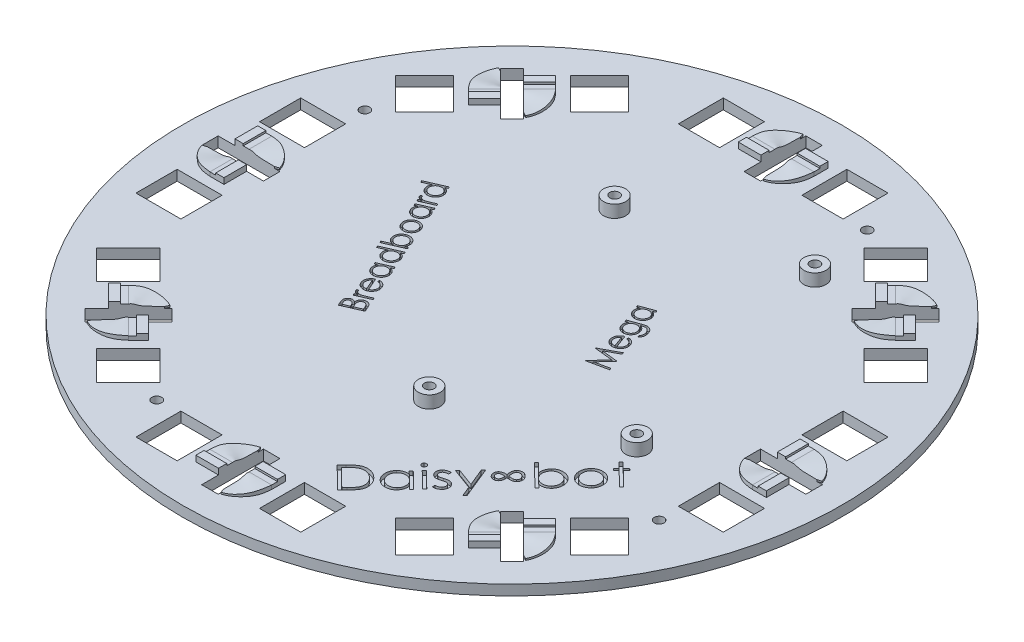
SolidWorks part; units mm, degrees
ref_plane "Front" through (0, 0, 0) normal (0, 0, 1) x (1, 0, 0)
ref_plane "Top" through (0, 0, 0) normal (0, 1, 0) x (1, 0, 0)
ref_plane "Right" through (0, 0, 0) normal (1, 0, 0) x (0, 0, -1)
sketch "Sketch1" plane through (0, 0, 0) normal (0, 1, 0) x (1, 0, 0)
  circle A0 centre (0, 0) radius 101.6
  dimension "D1" = 203.2
extrude "Boss-Extrude1" add sketch "Sketch1" along normal blind 3.175 contours A0
sketch "Sketch2" plane through (0, 3.175, 0) normal (0, 1, 0) x (1, 0, 0)
  line L1 (-2.54, -93.1333) -> (2.54, -93.1333)
  line L2 (-2.54, -93.1333) -> (-2.54, -74.0833)
  line L3 (-2.54, -74.0833) -> (2.54, -74.0833)
  line L4 (2.54, -93.1333) -> (2.54, -74.0833)
  point P4 (0, -74.0833)
  dimension "D1" = 5.08
  dimension "D2" = 19.05
  dimension "D3" = 93.1333
extrude "Cut-Extrude1" cut sketch "Sketch2" against normal up to next and the other way through all contours L1 L4 L3 L2
sketch "Sketch4" plane through (0, 3.175, 0) normal (0, 1, 0) x (1, 0, 0)
  line L0 (0, -83.6083) -> (-2.9434, -74.5495) construction
  line L1 (-2.9434, -74.5495) -> (0, -83.6083) construction
  line L2 (0, -83.6083) -> (-5.5987, -75.9024) construction
  line L3 (0, -83.6083) -> (-7.7059, -78.0097) construction
  line L4 (0, -83.6083) -> (-9.0588, -80.6649) construction
  line L5 (0, -83.6083) -> (-9.525, -83.6083) construction
  line L9 (2.54, -74.0833) -> (-2.54, -74.0833) construction
  line L10 (2.54, -74.0833) -> (2.54, -93.1333) construction
  line L11 (-2.54, -74.0833) -> (-2.54, -93.1333) construction
  line L12 (2.54, -93.1333) -> (-2.54, -93.1333) construction
  circle A0 centre (0, -83.6083) radius 9.525 construction
  point P16 (0, -74.0833)
  point P19 (2.54, -83.6083)
  dimension "D1" = 18
  dimension "D2" = 18
  dimension "D3" = 18
  dimension "D4" = 18
  dimension "D5" = 18
ref_plane "Plane1" through (-24.5719, 0, 7.9839) normal (0.9511, 0, -0.309) x (-0.309, 0, -0.9511)
ref_plane "Plane2" through (-39.7581, 0, 28.886) normal (0.809, 0, -0.5878) x (-0.5878, 0, -0.809)
ref_plane "Plane3" through (-39.7581, 0, 54.7224) normal (0.5878, 0, -0.809) x (-0.809, 0, -0.5878)
ref_plane "Plane4" through (-24.5719, 0, 75.6244) normal (0.309, 0, -0.9511) x (-0.9511, 0, -0.309)
ref_plane "Plane5" through (0, 0, 83.6083) normal (0, 0, -1) x (-1, 0, 0)
sketch "Sketch5" plane through (-24.5719, 0, 7.9839) normal (0.9511, 0, -0.309) x (-0.309, 0, -0.9511)
  line L0 (-69.6725, 3.175) -> (-87.7902, 3.175) construction
  line L1 (-71.2966, 3.175) -> (-69.9913, 3.175)
  line L2 (-71.2966, 3.175) -> (-71.2966, 3.683)
  line L3 (-71.2966, 3.683) -> (-69.9913, 3.683)
  line L4 (-69.9913, 3.175) -> (-69.9913, 3.683)
  dimension "D2" = 0.508
sketch "Sketch6" plane through (-39.7581, 0, 28.886) normal (0.809, 0, -0.5878) x (-0.5878, 0, -0.809)
  line L0 (-58.4417, 3.175) -> (-73.8535, 3.175) construction
  line L1 (-63.3193, 3.175) -> (-58.1156, 3.175)
  line L2 (-63.3193, 3.175) -> (-63.3193, 3.775)
  line L3 (-63.3193, 3.775) -> (-58.1156, 3.775)
  line L4 (-58.1156, 3.175) -> (-58.1156, 3.775)
  dimension "D2" = 0.6
sketch "Sketch7" plane through (-39.7581, 0, 54.7224) normal (0.5878, 0, -0.809) x (-0.809, 0, -0.5878)
  line L0 (-41.4902, 3.175) -> (-52.6875, 3.175) construction
  line L1 (-46.0041, 3.175) -> (-39.6187, 3.175)
  line L2 (-46.0041, 3.175) -> (-46.0041, 4.075)
  line L3 (-46.0041, 4.075) -> (-39.6187, 4.075)
  line L4 (-39.6187, 3.175) -> (-39.6187, 4.075)
  dimension "D2" = 0.9
sketch "Sketch10" plane through (-24.5719, 0, 75.6244) normal (0.309, 0, -0.9511) x (-0.9511, 0, -0.309)
  line L0 (-25.8364, 3.175) -> (-16.7776, 3.175) construction
  line L1 (-23.1657, 3.175) -> (-16.3114, 3.175)
  line L2 (-23.1657, 3.175) -> (-23.1657, 4.375)
  line L3 (-23.1657, 4.375) -> (-16.3114, 4.375)
  line L4 (-16.3114, 3.175) -> (-16.3114, 4.375)
  dimension "D3" = 1.2
sketch "Sketch11" plane through (0, 0, 83.6083) normal (0, 0, -1) x (-1, 0, 0)
  line L0 (0, 3.175) -> (9.525, 3.175) construction
  line L1 (2.54, 3.175) -> (9.525, 3.175)
  line L2 (2.54, 3.175) -> (2.54, 4.375)
  line L3 (2.54, 4.375) -> (9.525, 4.375)
  line L4 (9.525, 3.175) -> (9.525, 4.375)
  dimension "D3" = 1.2
loft "Loft1" add profiles "Sketch5", "Sketch6", "Sketch7", "Sketch10", "Sketch11" connector at (-2.54, 3.683, 75.791) connector at (-2.54, 3.775, 80.1123) connector at (-2.54, 4.075, 81.7629) connector at (-2.54, 4.375, 82.783) connector at (-2.54, 4.375, 83.6083)
sketch "Sketch13" plane through (-104.9799, 0, 83.6083) normal (0, 0, -1) x (-1, 0, 0)
  line L6 (-95.4549, 3.175) -> (-102.4399, 3.175)
  line L7 (-95.4549, 3.175) -> (-95.4549, 4.375)
  line L8 (-95.4549, 4.375) -> (-102.4399, 4.375)
  line L9 (-102.4399, 3.175) -> (-102.4399, 4.375)
extrude "Boss-Extrude4" add sketch "Sketch13" against normal blind 1.7907
sketch "Sketch25" plane through (0, 0, 85.399) normal (0, 0, 1) x (1, 0, 0)
  line L0 (-9.525, 4.375) -> (-2.54, 4.375) construction
  line L1 (-9.525, 3.175) -> (-2.54, 3.175)
  line L2 (-9.525, 3.175) -> (-9.525, 4.975)
  line L3 (-9.525, 4.975) -> (-2.54, 4.975)
  line L4 (-2.54, 3.175) -> (-2.54, 4.975)
  dimension "D1" = 0.6
extrude "Boss-Extrude5" add sketch "Sketch25" along normal blind 2.54
sketch "Sketch14" plane through (-2.54, 0, 0) normal (1, 0, 0) x (0, 0, -1)
  line L0 (-83.6083, 3.175) -> (-83.6083, 0) construction
  line L1 (-74.0833, 0) -> (-93.1333, 0) construction
ref_plane "Plane6" through (0, 0, 0) normal (1, 0, 0) x (0, 0, -1)
sketch "Sketch15" plane through (0, 0, 0) normal (1, 0, 0) x (0, 0, -1)
  line L0 (-83.6083, 0) -> (-83.6083, 3.175) construction
pattern_circular "CirPattern1" count 2 over 360 about axis through (0, 0, 83.6083) along (0, 1, 0) of "Loft1", "Boss-Extrude5", "Boss-Extrude4" reverse direction yes
ref_axis "Axis1" through (0, 50, 0) along (0, -1, 0)
pattern_circular "CirPattern5" count 8 over 360 about axis through (0, 50, 0) along (0, -1, 0) of "CirPattern1", "Cut-Extrude1"
sketch "Sketch18" plane through (0, 3.175, 0) normal (0, 1, 0) x (1, 0, 0)
  line L0 (-12.3739, 44.0137) -> (36.5149, 57.7582) construction
  line L1 (-12.3739, 44.0137) -> (9.9679, -35.4555) construction
  line L2 (36.5149, 57.7582) -> (36.8586, 56.5356) construction
  line L3 (54.6967, -16.2402) -> (8.2378, -29.3015) construction
  line L4 (0, -101.6) -> (0, 101.6) construction
  line L5 (0, -1.7463) -> (0, 1.7463) construction
  line L6 (-101.6, 0) -> (101.6, 0) construction
  line L7 (36.8586, 56.5356) -> (54.6967, -16.2402) construction
  circle A0 centre (-12.3739, 44.0137) radius 3.405
  circle A1 centre (9.9679, -35.4555) radius 3.405
  circle A2 centre (54.6967, -16.2402) radius 3.405
  circle A3 centre (36.8586, 56.5356) radius 3.405
  circle A4 centre (9.9679, -35.4555) radius 1.5
  circle A5 centre (-12.3739, 44.0137) radius 1.5
  circle A6 centre (36.8586, 56.5356) radius 1.5
  circle A7 centre (54.6967, -16.2402) radius 1.5
  circle A8 centre (0, 0) radius 101.6 construction
  dimension "D7" = 1.905
  dimension "D8" = 3
  dimension "D9" = 1.27
  dimension "D1" = 82.55
  dimension "D2" = 74.93
  dimension "D3" = 50.8
  dimension "D4" = 15.703
  dimension "D5" = 36.83
  dimension "D10" = 48.26
sketch "Sketch19" plane through (0, 3.175, 0) normal (0, 1, 0) x (1, 0, 0)
  line L0 (-32.0765, -77.4396) -> (0, 0) construction
  line L1 (0, -101.6) -> (0, 101.6) construction
  circle A1 centre (-32.0765, -77.4396) radius 1.5
  circle A4 centre (0, 0) radius 101.6 construction
  dimension "D4" = 3
  dimension "D6" = 83.82
  dimension "D5" = 22.5
extrude "Cut-Extrude2" cut sketch "Sketch19" against normal through all
pattern_circular "CirPattern7" count 4 over 360 about axis through (0, 50, 0) along (0, -1, 0) of "Cut-Extrude2"
extrude "Boss-Extrude3" add sketch "Sketch18" along normal blind 3.81
sketch "Sketch23" plane through (0, 3.175, 0) normal (0, 1, 0) x (1, 0, 0)
  line L9 (-2.54, -87.939) -> (-2.54, -93.1333) construction
  line L10 (-25.4, -76.6805) -> (-12.7, -76.6805)
  line L11 (-25.4, -76.6805) -> (-25.4, -90.5362)
  line L16 (-25.4, -90.5362) -> (-12.7, -90.5362)
  line L17 (-12.7, -76.6805) -> (-12.7, -90.5362)
  line L19 (2.54, -74.0833) -> (2.54, -79.2776) construction
  line L20 (0, -50) -> (0, 50) construction
  line L21 (12.7, -76.6805) -> (12.7, -90.5362)
  line L22 (25.4, -90.5362) -> (12.7, -90.5362)
  line L23 (25.4, -76.6805) -> (25.4, -90.5362)
  line L24 (25.4, -76.6805) -> (12.7, -76.6805)
  point P8 (-2.54, -90.5362)
  point P9 (2.54, -76.6805)
  dimension "D1" = 12.7
  dimension "D2" = 10.16
extrude "Cut-Extrude6" cut sketch "Sketch23" against normal through all
pattern_circular "CirPattern8" count 8 over 360 about axis through (0, 50, 0) along (0, -1, 0) of "Cut-Extrude6"
sketch "Sketch17" plane through (0, 3.175, 0) normal (0, 1, 0) x (1, 0, 0)
  line L0 (19.0413, -74.398) -> (63.1398, -28.708) construction
  dimension "D2" = 74.398
  dimension "D1" = 63.5
  dimension "D3" = 69.3598
  dimension "D4" = 76.796
sketch "Sketch16" plane through (0, 3.175, 0) normal (0, 1, 0) x (1, 0, 0)
  line L0 (19.0413, -74.398) -> (63.1398, -28.708) construction
  line L1 (25.4, -76.6805) -> (12.7, -76.6805) construction
  text T0 "Daisy∞bot\r\n" font "Century Gothic" height in points 36
extrude "Cut-Extrude4" cut sketch "Sketch16" against normal blind 1.27
sketch "Sketch22" plane through (0, 3.175, 0) normal (0, 1, 0) x (1, 0, 0)
  line L0 (-44.1287, 25.1735) -> (-20.5694, -28.6741) construction
  text T0 "Breadboard"
extrude "Cut-Extrude5" cut sketch "Sketch22" against normal blind 1.27
sketch "Sketch24" plane through (0, 3.175, 0) normal (0, 1, 0) x (1, 0, 0)
  line L0 (29.8571, 0) -> (21.0896, 23.8389) construction
  text T0 "Mega"
  dimension "D1" = 28.022
  dimension "D2" = 25.4
  dimension "D3" = 29.8571
extrude "Cut-Extrude7" cut sketch "Sketch24" against normal blind 1.27
